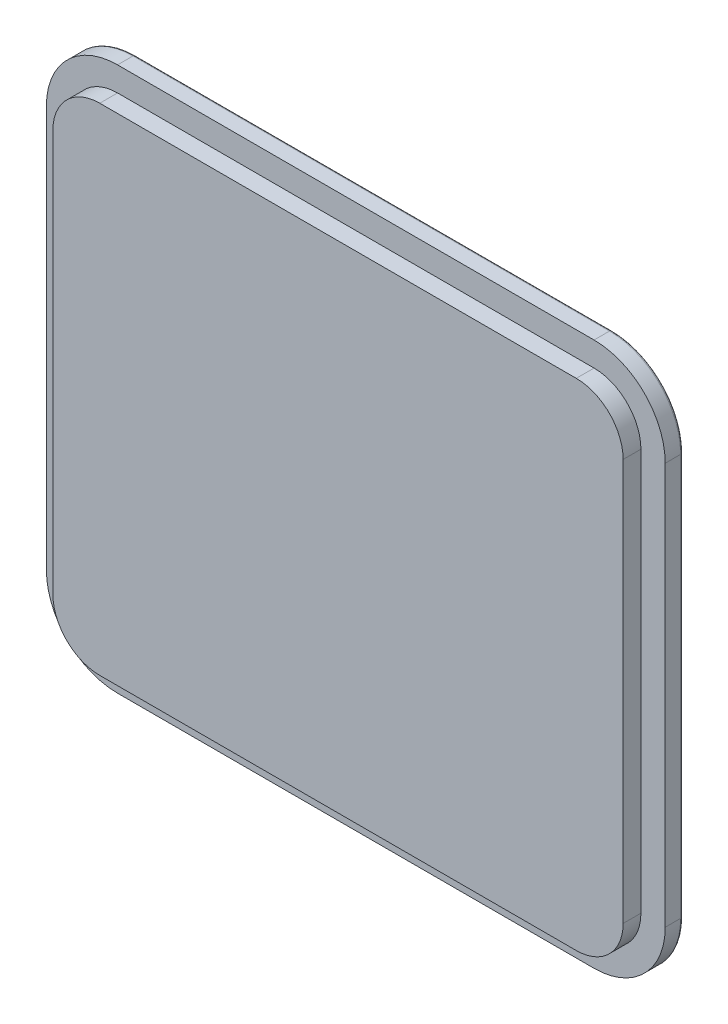
SolidWorks part; units mm, degrees
ref_plane "Front Plane" through (0, 0, 0) normal (0, 0, 1) x (1, 0, 0)
ref_plane "Top Plane" through (0, 0, 0) normal (0, 1, 0) x (1, 0, 0)
ref_plane "Right Plane" through (0, 0, 0) normal (1, 0, 0) x (0, 0, -1)
sketch "Sketch3" plane through (0, 0, 0) normal (0, 0, 1) x (1, 0, 0)
  line L0 (-27.4043, 19.1994) -> (-27.4043, -14.6815)
  line L1 (-21.4043, -20.6815) -> (18.7742, -20.6815)
  line L2 (24.7742, -14.6815) -> (24.7742, 19.1994)
  line L3 (18.7742, 25.1994) -> (-21.4043, 25.1994)
  line L4 (-25.3543, 19.1994) -> (-25.3543, -14.6815)
  line L5 (-21.4043, -18.6315) -> (18.7742, -18.6315)
  line L6 (22.7242, -14.6815) -> (22.7242, 19.1994)
  line L7 (18.7742, 23.1494) -> (-21.4043, 23.1494)
  arc A0 (-27.4043, -14.6815) -> (-21.4043, -20.6815) centre (-21.4043, -14.6815) ccw
  arc A1 (18.7742, -20.6815) -> (24.7742, -14.6815) centre (18.7742, -14.6815) ccw
  arc A2 (24.7742, 19.1994) -> (18.7742, 25.1994) centre (18.7742, 19.1994) ccw
  arc A3 (-27.4043, 19.1994) -> (-21.4043, 25.1994) centre (-21.4043, 19.1994) cw
  arc A4 (-25.3543, -14.6815) -> (-21.4043, -18.6315) centre (-21.4043, -14.6815) ccw
  arc A5 (18.7742, -18.6315) -> (22.7242, -14.6815) centre (18.7742, -14.6815) ccw
  arc A6 (22.7242, 19.1994) -> (18.7742, 23.1494) centre (18.7742, 19.1994) ccw
  arc A7 (-25.3543, 19.1994) -> (-21.4043, 23.1494) centre (-21.4043, 19.1994) cw
  point P26 (0, 0)
  point P27 (0, 0)
  point P28 (0, 0)
  point P29 (0, 0)
  point P30 (0, 0)
  point P31 (0, 0)
  point P32 (0, 0)
  point P33 (0, 0)
  point P34 (0, 0)
  dimension "D1" = 6
  dimension "D2" = 2.05
extrude "Boss-Extrude3" add sketch "Sketch3" along normal blind 3 contours L7 A7 L4 A4 L5 A5 L6 A6
extrude "Boss-Extrude4" add sketch "Sketch3<4>" along normal blind 1.5
sketch "Sketch3<4>" plane through (0, 0, 0) normal (0, 0, 1) x (1, 0, 0) same geometry as "Sketch3"
fillet "Fillet1" radius 0.2 8 edges at (23.0169, 23.4421, 0) (24.7742, 2.259, 0) (23.0169, -18.9241, 0) (-1.315, -20.6815, 0) (-25.6469, -18.9241, 0) (-27.4043, 2.259, 0) (-25.6469, 23.4421, 0) (-1.315, 25.1994, 0)
